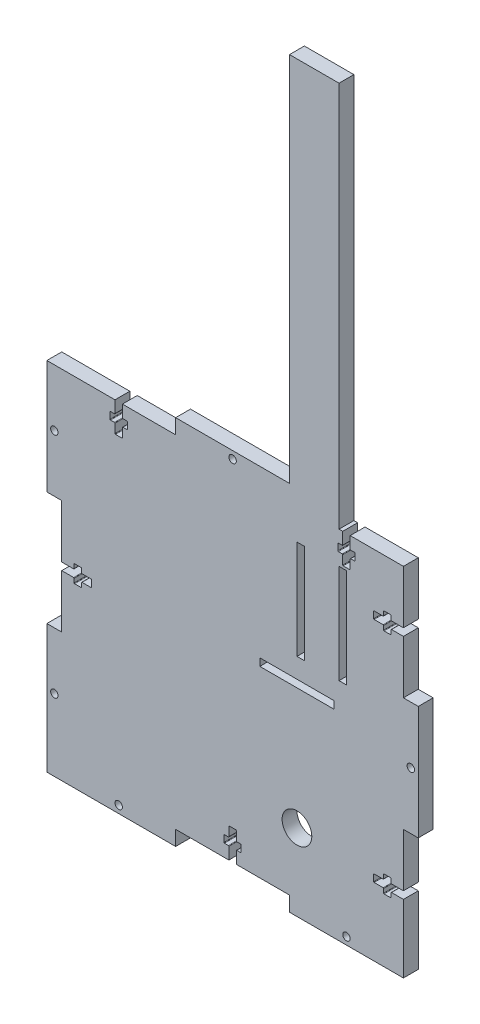
SolidWorks part; units mm, degrees
ref_plane "Front Plane" through (0, 0, 0) normal (0, 0, 1) x (1, 0, 0)
ref_plane "Top Plane" through (0, 0, 0) normal (0, 1, 0) x (1, 0, 0)
ref_plane "Right Plane" through (0, 0, 0) normal (1, 0, 0) x (0, 0, -1)
sketch "Sketch1" plane through (0, 0, 0) normal (0, 0, 1) x (1, 0, 0)
  line L0 (-69, 69) -> (-23, 69)
  line L5 (-75, -75) -> (75, -75) construction
  line L6 (-75, -75) -> (-75, 75) construction
  line L7 (-75, 75) -> (75, 75) construction
  line L8 (75, -75) -> (75, 75) construction
  line L9 (75, 23) -> (69, 23)
  line L10 (69, -23) -> (75, -23)
  line L11 (-69, -69) -> (69, -69) construction
  line L12 (-69, -69) -> (-69, 69) construction
  line L13 (-69, 69) -> (69, 69) construction
  line L14 (69, -69) -> (69, 69) construction
  line L15 (-69, -69) -> (69, 69) construction
  line L16 (69, -69) -> (69, -23)
  line L17 (-23, 69) -> (-23, 75)
  line L18 (-23, 75) -> (23, 75)
  line L19 (23, 75) -> (23, 69)
  line L20 (23, 69) -> (69, 69)
  line L21 (75, -23) -> (75, 23)
  line L22 (69, 23) -> (69, 69)
  line L23 (-75, 23) -> (-69, 23)
  line L24 (-69, 69) -> (-75, 69)
  line L25 (-75, 69) -> (-75, 23)
  line L26 (69, -69) -> (69, -75)
  line L27 (69, -75) -> (23, -75)
  line L28 (23, -75) -> (23, -69)
  line L29 (23, -69) -> (-23, -69)
  line L30 (-23, -69) -> (-23, -75)
  line L31 (-23, -75) -> (-69, -75)
  line L32 (-69, -75) -> (-69, -69) construction
  line L33 (-69, 23) -> (-69, -23)
  line L34 (-69, -23) -> (-75, -23)
  line L35 (-75, -23) -> (-75, -69)
  line L36 (-75, -69) -> (-69, -69) construction
  line L37 (-46, 69) -> (-46, -75) construction
  line L38 (-69, 69) -> (69, -69) construction
  line L39 (-75, -75) -> (-69, -75)
  line L40 (-75, -75) -> (-75, -69)
  point P0 (0, 0)
  point P6 (-7, -7)
  point P26 (0, -75)
  point P27 (-75, 0)
  dimension "D1" = 150
  dimension "D2" = 150
  dimension "D5" = 46
  dimension "D3" = 6
  dimension "D6" = 6
  dimension "D7" = 6
extrude "Box Side" add sketch "Sketch1" along normal blind 6
sketch "Sketch2" plane through (0, 0, 6) normal (0, 0, 1) x (1, 0, 0)
  line L0 (23, 72) -> (-23, 72) construction
  line L1 (23, 75) -> (23, 69) construction
  line L2 (-23, 69) -> (-23, 75) construction
  line L3 (-46, 69) -> (-46, -75) construction
  line L5 (0, 75) -> (0, 69) construction
  line L6 (-23, 75) -> (23, 75) construction
  line L7 (-69, 69) -> (69, 69) construction
  line L16 (-46, 69) -> (-46, -75) construction
  line L21 (0, -69) -> (0, 69) construction
  line L35 (-69, 69) -> (-23, 69) construction
  line L36 (-44.5, 69) -> (-44.5, 64.2)
  line L37 (-44.3, 64) -> (-42.7, 64)
  line L38 (-42.5, 63.8) -> (-42.5, 61.2)
  line L39 (-42.7, 61) -> (-44.3, 61)
  line L40 (-44.5, 60.8) -> (-44.5, 57.2)
  line L46 (-44.7, 57) -> (-47.3, 57)
  line L48 (-44.5, 69) -> (-47.5, 69)
  line L51 (-47.5, 60.8) -> (-47.5, 57.2)
  line L52 (-49.3, 61) -> (-47.7, 61)
  line L53 (-49.5, 63.8) -> (-49.5, 61.2)
  line L54 (-47.7, 64) -> (-49.3, 64)
  line L55 (-47.5, 69) -> (-47.5, 64.2)
  line L56 (47.5, 69) -> (47.5, 64.2)
  line L57 (47.7, 64) -> (49.3, 64)
  line L58 (49.5, 63.8) -> (49.5, 61.2)
  line L59 (49.3, 61) -> (47.7, 61)
  line L60 (47.5, 60.8) -> (47.5, 57.2)
  line L61 (44.5, 69) -> (47.5, 69)
  line L62 (44.7, 57) -> (47.3, 57)
  line L63 (44.5, 60.8) -> (44.5, 57.2)
  line L64 (42.7, 61) -> (44.3, 61)
  line L65 (42.5, 63.8) -> (42.5, 61.2)
  line L66 (44.3, 64) -> (42.7, 64)
  line L67 (44.5, 69) -> (44.5, 64.2)
  line L68 (-69, -69) -> (69, 69) construction
  line L69 (-69, -69) -> (69, 69) construction
  line L70 (75, 0) -> (69, 0) construction
  line L71 (72, 23) -> (72, -23) construction
  line L72 (69, 44.5) -> (64.2, 44.5)
  line L73 (64, 44.3) -> (64, 42.7)
  line L74 (63.8, 42.5) -> (61.2, 42.5)
  line L75 (61, 42.7) -> (61, 44.3)
  line L76 (60.8, 44.5) -> (57.2, 44.5)
  line L77 (57, 44.7) -> (57, 47.3)
  line L78 (69, 44.5) -> (69, 47.5)
  line L79 (60.8, 47.5) -> (57.2, 47.5)
  line L80 (61, 49.3) -> (61, 47.7)
  line L81 (63.8, 49.5) -> (61.2, 49.5)
  line L82 (64, 47.7) -> (64, 49.3)
  line L83 (69, 47.5) -> (64.2, 47.5)
  line L84 (69, -47.5) -> (64.2, -47.5)
  line L85 (64, -47.7) -> (64, -49.3)
  line L86 (63.8, -49.5) -> (61.2, -49.5)
  line L87 (61, -49.3) -> (61, -47.7)
  line L88 (60.8, -47.5) -> (57.2, -47.5)
  line L89 (69, -44.5) -> (69, -47.5)
  line L90 (57, -44.7) -> (57, -47.3)
  line L91 (60.8, -44.5) -> (57.2, -44.5)
  line L92 (61, -42.7) -> (61, -44.3)
  line L93 (63.8, -42.5) -> (61.2, -42.5)
  line L94 (64, -44.3) -> (64, -42.7)
  line L95 (69, -44.5) -> (64.2, -44.5)
  line L120 (-69, 69) -> (69, -69) construction
  line L121 (-69, 69) -> (69, -69) construction
  line L122 (-1.5, -69) -> (1.5, -69)
  line L123 (-23, -69) -> (23, -69) construction
  line L124 (1.5, -69) -> (1.5, -64.2)
  line L125 (1.7, -64) -> (3.3, -64)
  line L126 (3.5, -63.8) -> (3.5, -61.2)
  line L127 (3.3, -61) -> (1.7, -61)
  line L128 (1.5, -60.8) -> (1.5, -57.2)
  line L129 (1.3, -57) -> (-1.3, -57)
  line L130 (-1.5, -60.8) -> (-1.5, -57.2)
  line L131 (-3.3, -61) -> (-1.7, -61)
  line L132 (-3.5, -63.8) -> (-3.5, -61.2)
  line L133 (-1.7, -64) -> (-3.3, -64)
  line L134 (-1.5, -69) -> (-1.5, -64.2)
  line L135 (-69, -1.5) -> (-64.2, -1.5)
  line L136 (-64, -1.7) -> (-64, -3.3)
  line L137 (-63.8, -3.5) -> (-61.2, -3.5)
  line L138 (-61, -3.3) -> (-61, -1.7)
  line L139 (-60.8, -1.5) -> (-57.2, -1.5)
  line L140 (-57, 1.3) -> (-57, -1.3)
  line L141 (-60.8, 1.5) -> (-57.2, 1.5)
  line L142 (-61, 3.3) -> (-61, 1.7)
  line L143 (-63.8, 3.5) -> (-61.2, 3.5)
  line L144 (-64, 1.7) -> (-64, 3.3)
  line L145 (-69, 1.5) -> (-64.2, 1.5)
  line L146 (-69, -1.5) -> (-69, 1.5)
  line L147 (-69, -72) -> (-23, -72) construction
  line L148 (-23, 69) -> (-75, 69) construction
  line L149 (-23, -75) -> (-23, -69) construction
  line L150 (-69, -69) -> (-69, -75) construction
  line L151 (-75, -75) -> (-23, -75) construction
  circle A0 centre (0, 72) radius 1.5
  arc A1 (-44.5, 57.2) -> (-44.7, 57) centre (-44.7, 57.2) cw
  arc A2 (-44.3, 61) -> (-44.5, 60.8) centre (-44.3, 60.8) ccw
  arc A3 (-42.5, 61.2) -> (-42.7, 61) centre (-42.7, 61.2) cw
  arc A4 (-42.7, 64) -> (-42.5, 63.8) centre (-42.7, 63.8) cw
  arc A5 (-44.5, 64.2) -> (-44.3, 64) centre (-44.3, 64.2) ccw
  arc A6 (-47.5, 64.2) -> (-47.7, 64) centre (-47.7, 64.2) cw
  arc A7 (-49.3, 64) -> (-49.5, 63.8) centre (-49.3, 63.8) ccw
  arc A8 (-49.5, 61.2) -> (-49.3, 61) centre (-49.3, 61.2) ccw
  arc A9 (-47.7, 61) -> (-47.5, 60.8) centre (-47.7, 60.8) cw
  arc A10 (-47.5, 57.2) -> (-47.3, 57) centre (-47.3, 57.2) ccw
  arc A11 (47.5, 57.2) -> (47.3, 57) centre (47.3, 57.2) cw
  arc A12 (47.7, 61) -> (47.5, 60.8) centre (47.7, 60.8) ccw
  arc A13 (49.5, 61.2) -> (49.3, 61) centre (49.3, 61.2) cw
  arc A14 (49.3, 64) -> (49.5, 63.8) centre (49.3, 63.8) cw
  arc A15 (47.5, 64.2) -> (47.7, 64) centre (47.7, 64.2) ccw
  arc A16 (44.5, 64.2) -> (44.3, 64) centre (44.3, 64.2) cw
  arc A17 (42.7, 64) -> (42.5, 63.8) centre (42.7, 63.8) ccw
  arc A18 (42.5, 61.2) -> (42.7, 61) centre (42.7, 61.2) ccw
  arc A19 (44.3, 61) -> (44.5, 60.8) centre (44.3, 60.8) cw
  arc A20 (44.5, 57.2) -> (44.7, 57) centre (44.7, 57.2) ccw
  arc A21 (57.2, 44.5) -> (57, 44.7) centre (57.2, 44.7) cw
  arc A22 (61, 44.3) -> (60.8, 44.5) centre (60.8, 44.3) ccw
  arc A23 (61.2, 42.5) -> (61, 42.7) centre (61.2, 42.7) cw
  arc A24 (64, 42.7) -> (63.8, 42.5) centre (63.8, 42.7) cw
  arc A25 (64.2, 44.5) -> (64, 44.3) centre (64.2, 44.3) ccw
  arc A26 (64.2, 47.5) -> (64, 47.7) centre (64.2, 47.7) cw
  arc A27 (64, 49.3) -> (63.8, 49.5) centre (63.8, 49.3) ccw
  arc A28 (61.2, 49.5) -> (61, 49.3) centre (61.2, 49.3) ccw
  arc A29 (61, 47.7) -> (60.8, 47.5) centre (60.8, 47.7) cw
  arc A30 (57.2, 47.5) -> (57, 47.3) centre (57.2, 47.3) ccw
  arc A31 (57.2, -47.5) -> (57, -47.3) centre (57.2, -47.3) cw
  arc A32 (61, -47.7) -> (60.8, -47.5) centre (60.8, -47.7) ccw
  arc A33 (61.2, -49.5) -> (61, -49.3) centre (61.2, -49.3) cw
  arc A34 (64, -49.3) -> (63.8, -49.5) centre (63.8, -49.3) cw
  arc A35 (64.2, -47.5) -> (64, -47.7) centre (64.2, -47.7) ccw
  arc A36 (64.2, -44.5) -> (64, -44.3) centre (64.2, -44.3) cw
  arc A37 (64, -42.7) -> (63.8, -42.5) centre (63.8, -42.7) ccw
  arc A38 (61.2, -42.5) -> (61, -42.7) centre (61.2, -42.7) ccw
  arc A39 (61, -44.3) -> (60.8, -44.5) centre (60.8, -44.3) cw
  arc A40 (57.2, -44.5) -> (57, -44.7) centre (57.2, -44.7) ccw
  circle A41 centre (72, 0) radius 1.5
  arc A62 (1.5, -57.2) -> (1.3, -57) centre (1.3, -57.2) ccw
  arc A63 (1.7, -61) -> (1.5, -60.8) centre (1.7, -60.8) cw
  arc A64 (3.5, -61.2) -> (3.3, -61) centre (3.3, -61.2) ccw
  arc A65 (3.3, -64) -> (3.5, -63.8) centre (3.3, -63.8) ccw
  arc A66 (1.5, -64.2) -> (1.7, -64) centre (1.7, -64.2) cw
  arc A67 (-1.5, -64.2) -> (-1.7, -64) centre (-1.7, -64.2) ccw
  arc A68 (-3.3, -64) -> (-3.5, -63.8) centre (-3.3, -63.8) cw
  arc A69 (-3.5, -61.2) -> (-3.3, -61) centre (-3.3, -61.2) cw
  arc A70 (-1.7, -61) -> (-1.5, -60.8) centre (-1.7, -60.8) ccw
  arc A71 (-1.5, -57.2) -> (-1.3, -57) centre (-1.3, -57.2) cw
  arc A72 (-57.2, -1.5) -> (-57, -1.3) centre (-57.2, -1.3) ccw
  arc A73 (-61, -1.7) -> (-60.8, -1.5) centre (-60.8, -1.7) cw
  arc A74 (-61.2, -3.5) -> (-61, -3.3) centre (-61.2, -3.3) ccw
  arc A75 (-64, -3.3) -> (-63.8, -3.5) centre (-63.8, -3.3) ccw
  arc A76 (-64.2, -1.5) -> (-64, -1.7) centre (-64.2, -1.7) cw
  arc A77 (-64.2, 1.5) -> (-64, 1.7) centre (-64.2, 1.7) ccw
  arc A78 (-64, 3.3) -> (-63.8, 3.5) centre (-63.8, 3.3) cw
  arc A79 (-61.2, 3.5) -> (-61, 3.3) centre (-61.2, 3.3) cw
  arc A80 (-61, 1.7) -> (-60.8, 1.5) centre (-60.8, 1.7) ccw
  arc A81 (-57.2, 1.5) -> (-57, 1.3) centre (-57.2, 1.3) cw
  circle A82 centre (-46, -72) radius 1.5
  circle A83 centre (46, -72) radius 1.5
  circle A84 centre (-72, 46) radius 1.5
  circle A85 centre (-72, -46) radius 1.5
  point P6 (0, 72)
  point P38 (0, 0)
  point P56 (-46, 57)
  point P88 (46, 57)
  point P161 (57, 46)
  point P162 (57, -46)
  point P198 (0, -57)
  point P231 (-57, 0)
  point P234 (-42.5, 62.5)
  dimension "D1" = 3
  dimension "D2" = 0.2
  dimension "D8" = 0.2
  dimension "D14" = 3
  dimension "D4" = 3
  dimension "D7" = 1.5
  dimension "D10" = 3
  dimension "D12" = 1.5
  dimension "D9" = 12
  dimension "D11" = 5
  dimension "D13" = 7
  dimension "D3" = 12
  dimension "D5" = 7
  dimension "D6" = 5
extrude "Screw Cut-outs" cut sketch "Sketch2" against normal through all
sketch "Bearing Hole" plane through (0, 0, 6) normal (0, 0, 1) x (1, 0, 0)
  line L0 (20, -69) -> (50020, -69) construction
  line L1 (69, -44.5) -> (69, -23) construction
  line L4 (26, -41) -> (50026, -41) construction
  line L5 (26.5774, -47) -> (50026.5774, -47) construction
  line L8 (29, -52) -> (29, -50052) construction
  circle A0 centre (26, -44) radius 3 construction
  circle A1 centre (26, -54) radius 15 construction
  circle A2 centre (26, -44) radius 6
  dimension "D2" = 6
  dimension "D4" = 30
  dimension "D5" = 12
  dimension "D1" = 7
  dimension "D3" = 43
extrude "Shaft Hole" cut sketch "Bearing Hole" against normal through all
sketch "Sketch4" plane through (0, 0, 0) normal (0, 0, -1) x (-1, 0, 0)
  line L0 (-72, 1.5) -> (49928, 1.5) construction
  line L1 (-41, 8) -> (-11, 8)
  line L2 (-41, 8) -> (-41, 5)
  line L3 (-41, 5) -> (-11, 5)
  line L4 (-11, 8) -> (-11, 5)
  line L5 (-75, -23) -> (-75, 23) construction
  line L6 (-69, 23) -> (-69, 44.5) construction
  line L7 (-46, 56) -> (-43, 56)
  line L8 (-46, 56) -> (-46, 16)
  line L9 (-46, 16) -> (-43, 16)
  line L10 (-43, 56) -> (-43, 16)
  line L11 (-29, 56) -> (-26, 56)
  line L12 (-29, 56) -> (-29, 16)
  line L13 (-29, 16) -> (-26, 16)
  line L14 (-26, 56) -> (-26, 16)
  line L15 (-44.5, 69) -> (-23, 69) construction
  circle A1 centre (-72, 0) radius 1.5 construction
  point P18 (-29, 36)
  dimension "D1" = 3.5
  dimension "D2" = 30
  dimension "D3" = 3
  dimension "D4" = 34
  dimension "D5" = 14
  dimension "D6" = 23
  dimension "D7" = 13
  dimension "D8" = 3
  dimension "D9" = 40
extrude "Grooves" cut sketch "Sketch4" against normal up to surface (6 mm away) up to face at (32, -44, 6)
sketch "Sketch5" plane through (0, 69, 0) normal (0, 1, 0) x (1, 0, 0)
  line L0 (69, 0) -> (47.5, 0) construction
  line L1 (23, -6) -> (43, -6)
  line L2 (23, -6) -> (23, 0)
  line L3 (23, 0) -> (43, 0)
  line L4 (43, -6) -> (43, 0)
  line L5 (75, -6) -> (75, 0) construction
  dimension "D1" = 32
extrude "Boss-Extrude1" add sketch "Sketch5" along normal blind 156
equation "\"filletRadius\"=0.2"
equation "\"D8@Sketch2\"=\"filletRadius\""
equation "\"D2@Sketch2\"=\"filletRadius\""
equation "\"fingerWidth\"= 46"
equation "\"D5@Sketch1\"=\"fingerWidth\""
equation "\"wallThickness\"= 6"
equation "\"D3@Sketch1\" = \"wallThickness\""
equation "\"D6@Sketch1\" = \"wallThickness\""
equation "\"D7@Sketch1\" = \"wallThickness\""
equation "\"D1@Box Side\" = \"wallThickness\""
equation "\"M3\"= 3"
equation "\"D14@Sketch2\"=\"M3\""
equation "\"D1@Sketch2\"=\"M3\""
equation "\"D12@Sketch2\"=\"M3\"/2"
equation "\"nutThickness\"=3"
equation "\"D10@Sketch2\" = \"nutThickness\""
equation "\"boltLength\"= 12"
equation "\"D9@Sketch2\" = \"boltLength\""
equation "\"distanceToNut\"= 5"
equation "\"D11@Sketch2\" = \"distanceToNut\""
equation "\"D13@Sketch2\" = \"nutWidth\""
equation "\"D7@Sketch2\"=\"M3\"/2"
equation "\"D4@Sketch2\" = \"nutThickness\""
equation "\"D3@Sketch2\" = \"boltLength\""
equation "\"D5@Sketch2\" = \"nutWidth\""
equation "\"D6@Sketch2\" = \"distanceToNut\""
equation "\"sideLength\"=150"
equation "\"D1@Sketch1\"=\"sideLength\""
equation "\"D2@Sketch1\"=\"sideLength\""
equation "\"nutWidth\"=7"
